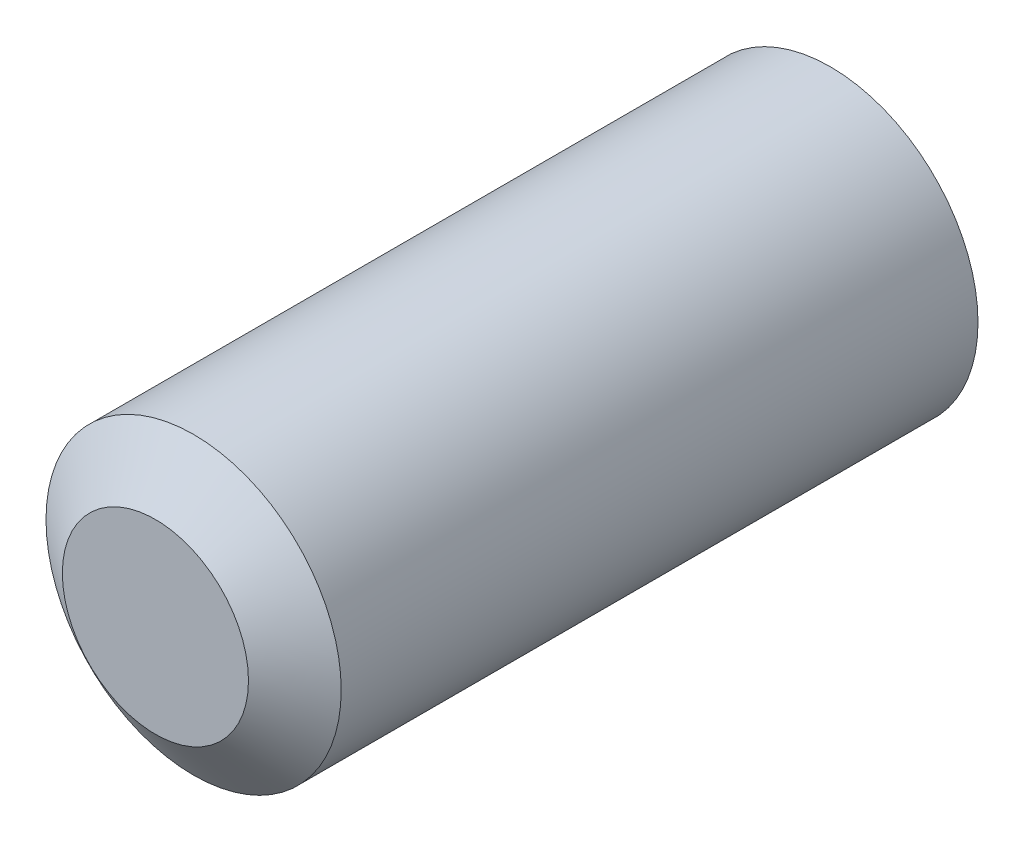
SolidWorks part; units mm, degrees
ref_plane "Front Plane" through (0, 0, 0) normal (0, 0, 1) x (1, 0, 0)
ref_plane "Top Plane" through (0, 0, 0) normal (0, 1, 0) x (1, 0, 0)
ref_plane "Right Plane" through (0, 0, 0) normal (1, 0, 0) x (0, 0, -1)
sketch "Sketch1" plane through (0, 0, 0) normal (0, 0, 1) x (1, 0, 0)
  circle A0 centre (0, 0) radius 2.0828
  dimension "D1" = 4.1656
extrude "Boss-Extrude1" add sketch "Sketch1" along normal blind 9.525
sketch "Sketch2" plane through (0, 0, 0) normal (1, 0, 0) x (0, 0, -1)
  line L0 (-9.525, 2.0828) -> (-9.525, 1.3132)
  line L1 (-9.525, 2.0828) -> (-9.525, -2.0828) construction
  line L2 (-9.525, 1.3132) -> (-8.9862, 2.0828)
  line L3 (0, 2.0828) -> (-9.525, 2.0828) construction
  line L4 (-8.9862, 2.0828) -> (-9.525, 2.0828)
  line L5 (0, 0) -> (-9.525, 0) construction
  dimension "D1" = 0.7696
  dimension "D2" = 55
revolve "Cut-Revolve1" cut sketch "Sketch2" angle 360 about L5
sketch "Sketch3" [suppressed] plane through (0, 0, 0) normal (0, 0, 1) x (1, 0, 0)
  circle A0 centre (0, 0) radius 3.9624
  dimension "D1" = 7.9248
extrude "Boss-Extrude2" [suppressed] add sketch "Sketch3" against normal blind 4.1656
sketch "Sketch4" [suppressed] plane through (0, 0, 0) normal (0, 0, 1) x (1, 0, 0)
  line L1 (0, -2.0622) -> (1.7859, -1.0311)
  line L2 (1.7859, -1.0311) -> (1.7859, 1.0311)
  line L3 (1.7859, 1.0311) -> (0, 2.0622)
  line L4 (0, 2.0622) -> (-1.7859, 1.0311)
  line L5 (-1.7859, 1.0311) -> (-1.7859, -1.0311)
  line L6 (-1.7859, -1.0311) -> (0, -2.0622)
  circle A0 centre (0, 0) radius 1.7859 construction
  dimension "D1" = 3.5719
extrude "Cut-Extrude1" [suppressed] cut sketch "Sketch4" along normal blind 2.6789 from surface
sketch "Sketch5" [suppressed] plane through (0, 0, -4.1656) normal (0, 0, -1) x (-1, 0, 0)
  circle A0 centre (0, 0) radius 2.0622
extrude "Cut-Extrude2" [suppressed] cut sketch "Sketch5" against normal through all draft 45
chamfer "Chamfer1" [suppressed] distance 0.3962 angle 45
sketch "Sketch6" [suppressed] plane through (0, 0, 0) normal (1, 0, 0) x (0, 0, -1)
  line L0 (0, 2.0828) -> (0, 4.5593)
  line L1 (0, 2.0828) -> (-3.5157, 2.0828)
  line L2 (0, 4.5593) -> (-0.2845, 4.5593)
  line L3 (-0.2845, 4.5593) -> (-2.8448, 2.3336)
  line L4 (0, 2.0828) -> (-8.9862, 2.0828) construction
  line L5 (0, 0) -> (-9.525, 0) construction
  line L6 (0, -2.0828) -> (0, 2.0828) construction
  line L7 (-9.525, 1.3132) -> (-9.525, -1.3132) construction
  arc A0 (-3.5157, 2.0828) -> (-2.8448, 2.3336) centre (-3.5157, 3.1055) ccw
  point P4 (0, 0)
  dimension "D1" = 4.5593
  dimension "D2" = 0.2845
  dimension "D3" = 2.8448
  dimension "D4" = 41
revolve "Revolve1" [suppressed] add sketch "Sketch6" angle 360 about L5
sketch "Sketch7" [suppressed] plane through (0, 0, 0) normal (0, 0, -1) x (-1, 0, 0)
  line L1 (-1.5875, -0.9165) -> (0, -1.8331)
  line L2 (0, -1.8331) -> (1.5875, -0.9165)
  line L3 (1.5875, -0.9165) -> (1.5875, 0.9165)
  line L4 (1.5875, 0.9165) -> (0, 1.8331)
  line L5 (0, 1.8331) -> (-1.5875, 0.9165)
  line L6 (-1.5875, 0.9165) -> (-1.5875, -0.9165)
  circle A0 centre (0, 0) radius 1.5875 construction
  dimension "D1" = 3.175
extrude "Cut-Extrude3" [suppressed] cut sketch "Sketch7" against normal blind 2.2581
sketch "Sketch8" [suppressed] plane through (0, 0, 0) normal (0, 0, -1) x (-1, 0, 0)
  circle A0 centre (0, 0) radius 1.8331
extrude "Cut-Extrude4" [suppressed] cut sketch "Sketch8" against normal through all draft 45
sketch "Sketch10" [suppressed] plane through (0, 0, 0) normal (1, 0, 0) x (0, 0, -1)
  line L0 (0, 0) -> (0, 3.9624)
  line L1 (0, 3.9624) -> (0.2721, 3.9624)
  line L2 (0, 0) -> (0.6385, 0)
  line L3 (0.6385, 0) -> (1.3259, 1.1906)
  line L4 (1.3259, 1.1906) -> (2.2098, 1.1906)
  line L5 (2.2098, 1.1906) -> (2.2098, 1.6669)
  line L6 (0, 0) -> (-4.1183, 0) construction
  arc A1 (0.2721, 3.9624) -> (2.2098, 1.6669) centre (-2.0935, 0) cw
  dimension "D1" = 0.2721
  dimension "D2" = 3.9624
  dimension "D3" = 0.6385
  dimension "D4" = 120
  dimension "D5" = 1.1906
  dimension "D6" = 1.6669
  dimension "D7" = 0.8839
revolve "Revolve2" [suppressed] add sketch "Sketch10" angle 360 about L6
sketch "Sketch11" [suppressed] plane through (0, 0, -2.2098) normal (0, 0, -1) x (-1, 0, 0)
  line L1 (-1.1906, -0.6874) -> (0, -1.3748)
  line L2 (0, -1.3748) -> (1.1906, -0.6874)
  line L3 (1.1906, -0.6874) -> (1.1906, 0.6874)
  line L4 (1.1906, 0.6874) -> (0, 1.3748)
  line L5 (0, 1.3748) -> (-1.1906, 0.6874)
  line L6 (-1.1906, 0.6874) -> (-1.1906, -0.6874)
  circle A0 centre (0, 0) radius 1.1906 construction
extrude "Cut-Extrude5" [suppressed] cut sketch "Sketch11" against normal up to vertex
sketch "Sketch12" [suppressed] plane through (0, 0, -2.2098) normal (0, 0, -1) x (-1, 0, 0)
  circle A0 centre (0, 0) radius 1.3748
extrude "Cut-Extrude6" [suppressed] cut sketch "Sketch12" against normal through all draft 45
sketch "Sketch13" [suppressed] plane through (0, 0, 0) normal (1, 0, 0) x (0, 0, -1)
  line L0 (0, 0) -> (0, 3.429)
  line L1 (0, -2.0828) -> (0, 2.0828) construction
  line L2 (0, 3.429) -> (1.6288, 3.429)
  line L3 (1.6288, 3.429) -> (1.9844, 3.0734)
  line L4 (1.9844, 3.0734) -> (1.9844, 0)
  line L5 (1.9844, 0) -> (0, 0)
  line L6 (0, 0) -> (-6.666, 0) construction
  dimension "D1" = 1.9844
  dimension "D2" = 3.429
  dimension "D3" = 3.0734
  dimension "D4" = 1.6288
revolve "Revolve3" [suppressed] add sketch "Sketch13" angle 360 about L6
sketch "Sketch14" [suppressed] plane through (0, 0, -1.9844) normal (0, 0, -1) x (-1, 0, 0)
  line L1 (0, -1.1457) -> (0.9922, -0.5728)
  line L2 (0.9922, -0.5728) -> (0.9922, 0.5728)
  line L3 (0.9922, 0.5728) -> (0, 1.1457)
  line L4 (0, 1.1457) -> (-0.9922, 0.5728)
  line L5 (-0.9922, 0.5728) -> (-0.9922, -0.5728)
  line L6 (-0.9922, -0.5728) -> (0, -1.1457)
  circle A0 centre (0, 0) radius 0.9922 construction
  dimension "D1" = 1.9844
extrude "Cut-Extrude7" [suppressed] cut sketch "Sketch14" against normal blind 1.524
sketch "Sketch15" [suppressed] plane through (0, 0, -1.9844) normal (0, 0, -1) x (-1, 0, 0)
  circle A0 centre (0, 0) radius 1.1457
extrude "Cut-Extrude8" [suppressed] cut sketch "Sketch15" against normal through all draft 45
equation "\"Length\"= .375"
equation "\"D1@Boss-Extrude1\"=\"Length\""
